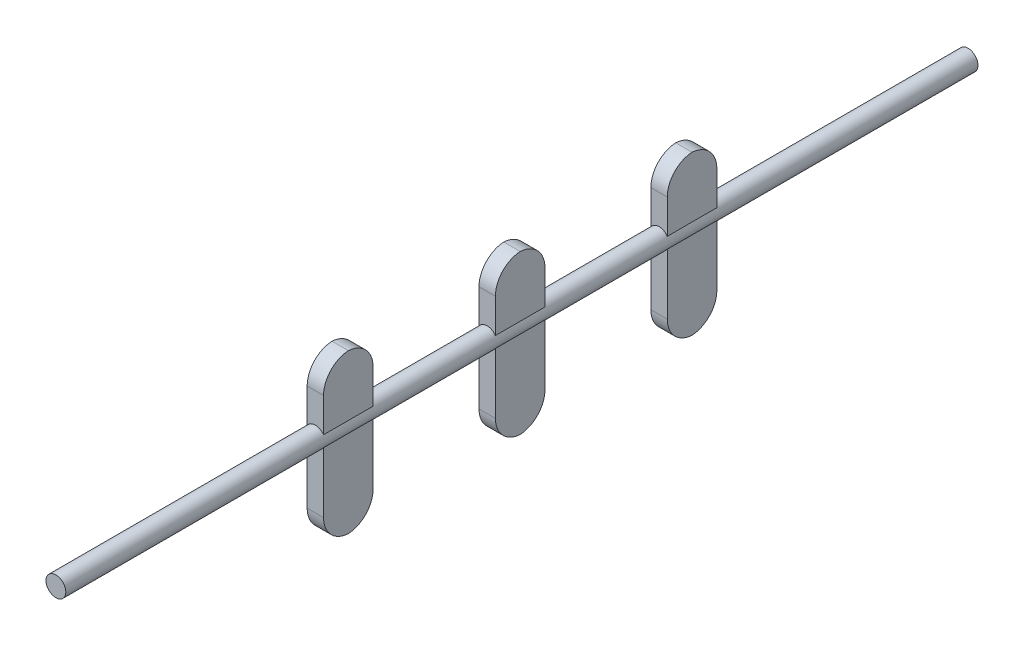
SolidWorks part; units mm, degrees
ref_plane "Front Plane" through (0, 0, 0) normal (0, 0, 1) x (1, 0, 0)
ref_plane "Top Plane" through (0, 0, 0) normal (0, 1, 0) x (1, 0, 0)
ref_plane "Right Plane" through (0, 0, 0) normal (1, 0, 0) x (0, 0, -1)
sketch "Sketch1" plane through (0, 0, 0) normal (0, 0, 1) x (1, 0, 0)
  circle A0 centre (0, 0) radius 4.7625
  dimension "D1" = 9.525
extrude "Boss-Extrude1" add sketch "Sketch1" along normal blind 438.15
ref_plane "Plane1" through (0, 0, 219.075) normal (0, 0, 1) x (1, 0, 0)
sketch "Sketch2" plane through (0, 0, 219.075) normal (0, 0, 1) x (1, 0, 0)
  line L1 (-3.9368, -44.45) -> (3.9368, -44.45)
  line L2 (-3.9368, -44.45) -> (-3.9368, 31.75)
  line L3 (-3.9368, 31.75) -> (3.9368, 31.75)
  line L4 (3.9368, -44.45) -> (3.9368, 31.75)
  point P0 (0, 0)
  dimension "D1" = 76.2
  dimension "D2" = 31.75
extrude "Boss-Extrude2" add sketch "Sketch2" along normal blind 11.9062 and the other way blind 11.9062
fillet "Fillet1" radius 12.7 4 edges at (0, 31.75, 207.1687) (0, 31.75, 230.9812) (0, -44.45, 230.9812) (0, -44.45, 207.1687)
pattern_linear "LPattern1" count 2 spacing 82.55 along (0, 0, 1) count 2 spacing 82.55 along (0, 0, -1) of "Boss-Extrude2", "Fillet1"
